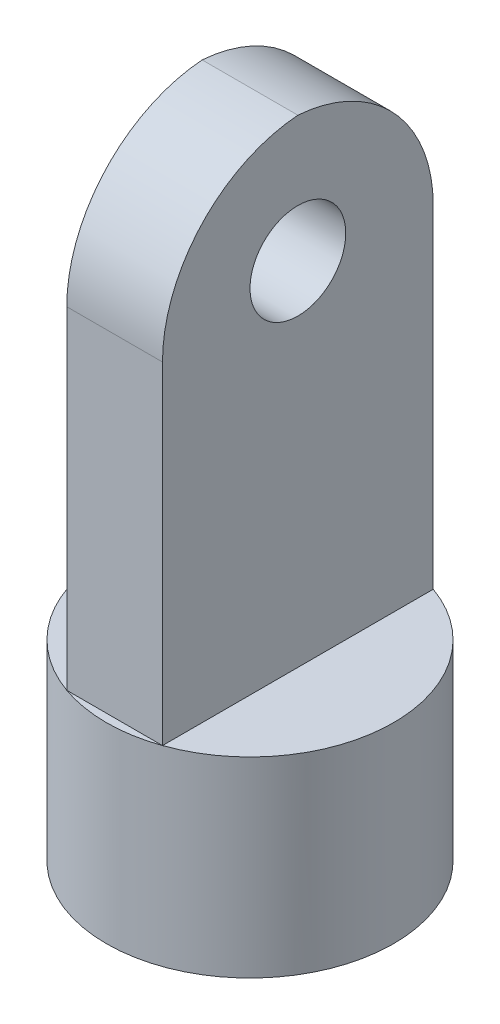
SolidWorks part; units mm, degrees
ref_plane "Front Plane" through (0, 0, 0) normal (0, 0, 1) x (1, 0, 0)
ref_plane "Top Plane" through (0, 0, 0) normal (0, 1, 0) x (1, 0, 0)
ref_plane "Right Plane" through (0, 0, 0) normal (1, 0, 0) x (0, 0, -1)
sketch "Sketch1" plane through (0, 0, 0) normal (0, 1, 0) x (1, 0, 0)
  circle A0 centre (0, 0) radius 7.5
  dimension "D1" = 15
extrude "Boss-Extrude1" add sketch "Sketch1" along normal blind 10
sketch "Sketch2" plane through (0, 0, 0) normal (0, -1, 0) x (1, 0, 0)
  circle A0 centre (0, 0) radius 6.25
  dimension "D1" = 12.5
extrude "Cut-Extrude2" cut sketch "Sketch2" against normal blind 7.5
sketch "Sketch3" plane through (0, 10, 0) normal (0, 1, 0) x (1, 0, 0)
  line L1 (-2.5, -7.0711) -> (2.5, -7.0711)
  line L2 (-2.5, -7.0711) -> (-2.5, 7.0711)
  line L3 (-2.5, 7.0711) -> (2.5, 7.0711)
  line L4 (2.5, -7.0711) -> (2.5, 7.0711)
  line L5 (-2.5, -7.0711) -> (2.5, 7.0711) construction
  line L6 (-2.5, 7.0711) -> (2.5, -7.0711) construction
  circle A0 centre (0, 0) radius 7.5 construction
  point P0 (0, 0)
  dimension "D1" = 5
extrude "Boss-Extrude2" add sketch "Sketch3" along normal blind 25
sketch "Sketch4" plane through (2.5, 0, 0) normal (1, 0, 0) x (0, 0, -1)
  circle A0 centre (0, 28.3918) radius 2.5
  dimension "D1" = 5
extrude "Cut-Extrude3" cut sketch "Sketch4" against normal blind 5
fillet "Fillet1" radius 7.65 2 edges at (0, 35, -7.0711) (0, 35, 7.0711)
